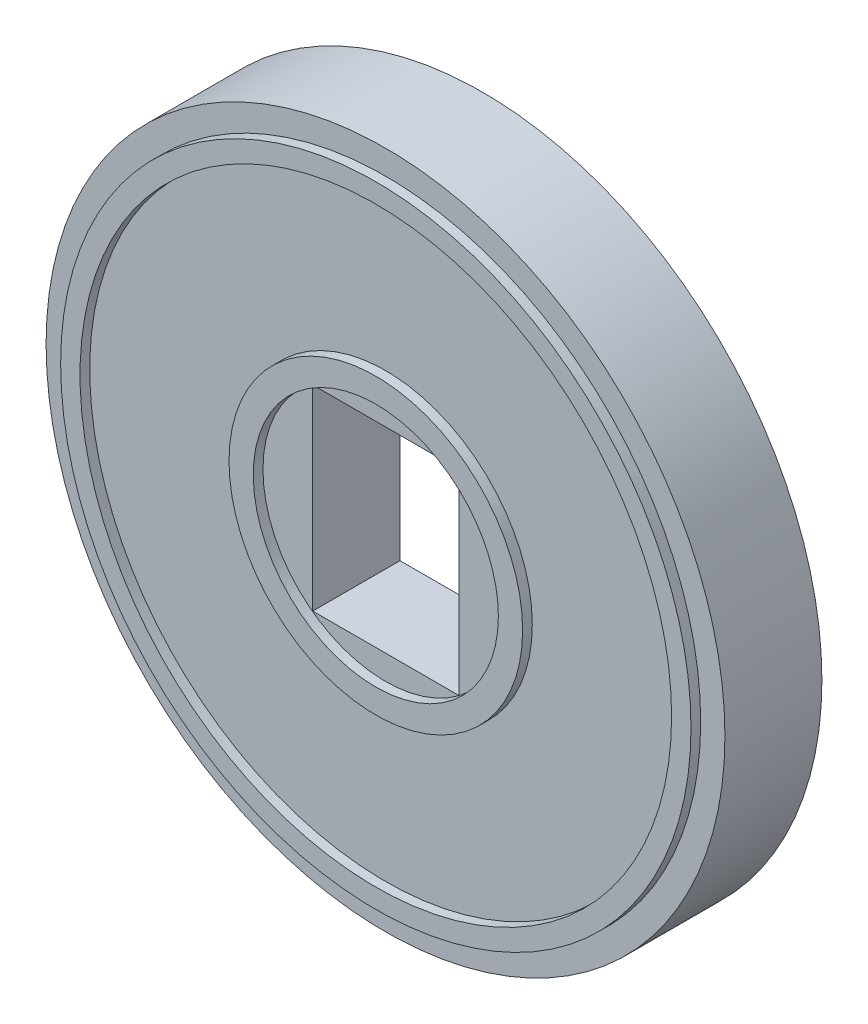
SolidWorks part; units mm, degrees
ref_plane "Ebene vorne" through (0, 0, 0) normal (0, 0, 1) x (1, 0, 0)
ref_plane "Ebene oben" through (0, 0, 0) normal (0, 1, 0) x (1, 0, 0)
ref_plane "Ebene rechts" through (0, 0, 0) normal (1, 0, 0) x (0, 0, -1)
sketch "Skizze1" plane through (0, 0, 0) normal (0, 0, 1) x (1, 0, 0)
  line L1 (-7.505, 10.1) -> (7.595, 10.1)
  line L2 (-7.505, 10.1) -> (-7.505, -10.1)
  line L3 (-7.505, -10.1) -> (7.595, -10.1)
  line L4 (7.595, 10.1) -> (7.595, -10.1)
  circle A0 centre (0, 0) radius 35
  dimension "D1" = 70
  dimension "D2" = 15.1
  dimension "D3" = 20.2
  dimension "D4" = 10.1
  dimension "D5" = 7.505
extrude "Aufsatz-Linear austragen1" add sketch "Skizze1" along normal blind 10 contours A0
extrude "Schnitt-Linear austragen1" cut sketch "Skizze1<3>" along normal blind 10 flip side to cut
sketch "Skizze1<3>" plane through (0, 0, 0) normal (0, 0, 1) x (1, 0, 0) same geometry as "Skizze1"
sketch "Skizze2" plane through (0, 0, 0) normal (0, 0, -1) x (-1, 0, 0)
  circle A0 centre (0, 25) radius 5.1
  dimension "D1" = 10.2
  dimension "D2" = 25
extrude "Schnitt-Linear austragen2" cut sketch "Skizze2" against normal blind 8 and the other way blind 1 contours A0
sketch "Skizze4" plane through (0, 0, 10) normal (0, 0, 1) x (1, 0, 0)
  circle A0 centre (0, 0) radius 12.637
  circle A1 centre (0, 0) radius 15.137
  dimension "D1" = 2.5
sketch "Skizze3" plane through (0, 0, 10) normal (0, 0, 1) x (1, 0, 0)
  circle A0 centre (0, 0) radius 32.5
  circle A1 centre (0, 0) radius 30.5
  point P5 (0, 0)
  dimension "D1" = 61
  dimension "D2" = 65
extrude "Aufsatz-Linear austragen2" add sketch "Skizze3" along normal blind 1
extrude "Aufsatz-Linear austragen3" add sketch "Skizze4" along normal blind 1
chamfer "Fase1" distance 1 angle 80 4 edges at (-7.505, 0, 0) (0.045, 10.1, 0) (7.595, 0, 0) (0.045, -10.1, 0) first distance on face at (-7.505, 0, 5) first distance on face at (0.045, 10.1, 5) first distance on face at (7.595, 0, 5) first distance on face at (0.045, -10.1, 5)
